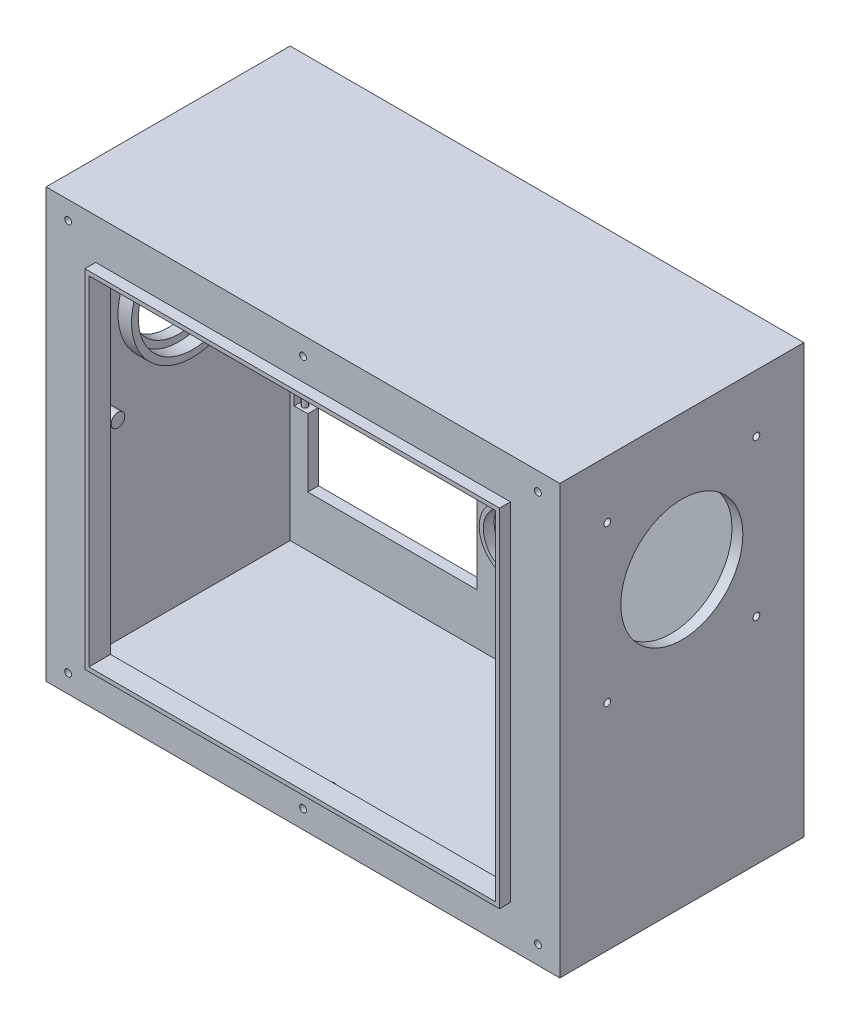
SolidWorks part; units mm, degrees
ref_plane "Alzado" through (0, 0, 0) normal (0, 0, 1) x (1, 0, 0)
ref_plane "Planta" through (0, 0, 0) normal (0, 1, 0) x (1, 0, 0)
ref_plane "Vista lateral" through (0, 0, 0) normal (1, 0, 0) x (0, 0, -1)
sketch "Croquis1" plane through (0, 0, 0) normal (0, 0, 1) x (1, 0, 0)
  line L0 (-189.5, 158) -> (189.5, 158)
  line L1 (-181.5, -150) -> (181.5, -150) construction
  line L2 (-181.5, -150) -> (-181.5, 150) construction
  line L3 (-181.5, 150) -> (181.5, 150) construction
  line L4 (181.5, -150) -> (181.5, 150) construction
  line L5 (-181.5, -150) -> (181.5, 150) construction
  line L6 (-181.5, 150) -> (181.5, -150) construction
  line L7 (189.5, -158) -> (189.5, 158)
  line L8 (-189.5, -158) -> (189.5, -158)
  line L9 (-189.5, -158) -> (-189.5, 158)
  point P0 (0, 0)
  dimension "D1" = 363
  dimension "D2" = 300
  dimension "D3" = 8
extrude "Saliente-Extruir1" add sketch "Croquis1" along normal blind 180
shell "Vaciado1" thickness 8 removed face at (0, 0, 180)
sketch "Croquis2" plane through (-189.5, 0, 0) normal (-1, 0, 0) x (0, 0, 1)
  line L0 (0, 158) -> (90, 158) construction
  line L1 (180, 158) -> (0, 158) construction
  circle A0 centre (90, 58) radius 35
extrude "Cortar-Extruir4" cut sketch "Croquis2" against normal blind 20 contours A0
sketch "Croquis4" plane through (-181.5, 0, 0) normal (1, 0, 0) x (0, 0, -1)
  circle A1 centre (-90, 58) radius 40
  circle A2 centre (-90, 58) radius 45
extrude "Saliente-Extruir4" add sketch "Croquis4" along normal blind 10
sketch "Croquis6" plane through (189.5, 0, 0) normal (1, 0, 0) x (0, 0, -1)
  line L0 (-90, 158) -> (-90, 58) construction
  line L1 (-180, 158) -> (0, 158) construction
  circle A0 centre (-90, 58) radius 45
  dimension "D1" = 90
extrude "Cortar-Extruir6" cut sketch "Croquis6" against normal blind 10 contours A0
sketch "Croquis7" plane through (0, 0, 8) normal (0, 0, 1) x (1, 0, 0)
  circle A3 centre (0, -53) radius 21
  circle A4 centre (0, -53) radius 24
  dimension "D1" = 42
  dimension "D2" = 48
extrude "Saliente-Extruir9" add sketch "Croquis7" along normal blind 18
ref_plane "Plano6" through (0, 0, 180) normal (0, 0, 1) x (1, 0, 0)
sketch "Croquis11" plane through (0, 0, 180) normal (0, 0, 1) x (1, 0, 0)
  line L1 (181.5, 150) -> (-181.5, 150)
  line L2 (181.5, 150) -> (181.5, -150)
  line L3 (181.5, -150) -> (-181.5, -150)
  line L4 (-181.5, 150) -> (-181.5, -150)
  line L5 (181.5, 150) -> (-181.5, -150) construction
  line L6 (181.5, -150) -> (-181.5, 150) construction
  line L7 (-150, 125) -> (150, 125)
  line L8 (-150, 125) -> (-150, -125)
  line L9 (-150, -125) -> (150, -125)
  line L10 (150, 125) -> (150, -125)
  line L11 (-150, 125) -> (150, -125) construction
  line L12 (-150, -125) -> (150, 125) construction
  point P0 (0, 0)
  point P7 (0, 0)
  dimension "D1" = 300
  dimension "D2" = 250
extrude "Saliente-Extruir10" add sketch "Croquis11" against normal blind 8
sketch "Croquis12" plane through (0, 0, 180) normal (0, 0, 1) x (1, 0, 0)
  line L1 (150, -125) -> (-150, -125)
  line L2 (150, -125) -> (150, 125)
  line L3 (150, 125) -> (-150, 125)
  line L4 (-150, -125) -> (-150, 125)
  line L5 (150, -125) -> (-150, 125) construction
  line L6 (150, 125) -> (-150, -125) construction
  line L7 (153, -128) -> (-153, -128)
  line L8 (153, -128) -> (153, 128)
  line L9 (153, 128) -> (-153, 128)
  line L10 (-153, -128) -> (-153, 128)
  line L11 (153, -128) -> (-153, 128) construction
  line L12 (153, 128) -> (-153, -128) construction
  point P0 (0, 0)
  point P8 (0, 0)
  dimension "D1" = 3
  dimension "D2" = 3
extrude "Saliente-Extruir11" add sketch "Croquis12" along normal blind 8
sketch "Croquis20" plane through (0, 0, 8) normal (0, 0, 1) x (1, 0, 0)
  circle A0 centre (0, -53) radius 18.5
  circle A1 centre (0, -53) radius 21
  circle A2 centre (0, -53) radius 21 construction
  dimension "D1" = 37
extrude "Saliente-Extruir19" add sketch "Croquis20" along normal blind 10
sketch "Croquis32" plane through (-181.5, 0, 0) normal (1, 0, 0) x (0, 0, -1)
  line L0 (-180, 158) -> (0, 158) construction
  line L1 (0, 158) -> (0, -158) construction
  line L2 (-35, 115.5) -> (-145, 115.5) construction
  line L3 (-35, 115.5) -> (-35, 0.5) construction
  line L4 (-35, 0.5) -> (-145, 0.5) construction
  line L5 (-145, 0.5) -> (-145, 115.5) construction
  circle A0 centre (-35, 115.5) radius 5
  circle A1 centre (-145, 115.5) radius 5
  circle A2 centre (-145, 0.5) radius 5
  circle A3 centre (-35, 0.5) radius 5
  dimension "D1" = 10
  dimension "D2" = 42.5
  dimension "D3" = 35
  dimension "D4" = 110
  dimension "D5" = 157.5
extrude "Saliente-Extruir22" add sketch "Croquis32" along normal blind 10
hole_wizard "Taladro roscado M63" positions "Croquis3D6" profile "Croquis26" tap size "M6" standard "DIN"
sketch3d "Croquis3D6"
  line L2 (-189.5, 0.5, 145) -> (-189.5, 115.5, 145) construction
  line L3 (-189.5, 0.5, 145) -> (-189.5, 0.5, 35) construction
  line L4 (-189.5, 0.5, 35) -> (-189.5, 115.5, 35) construction
  line L5 (-189.5, 115.5, 145) -> (-189.5, 115.5, 35) construction
  line L6 (-189.5, 0.5, 145) -> (-189.5, 115.5, 35) construction
  line L7 (-189.5, 0.5, 35) -> (-189.5, 115.5, 145) construction
  circle A1 centre (-189.5, 58, 90) radius 35 construction
  point P0 (-189.5, 115.5, 35)
  point P2 (-189.5, 115.5, 145)
  point P4 (-189.5, 0.5, 145)
  point P6 (-189.5, 0.5, 35)
  point P265 (-189.5, 58, 90)
  point P268 (-224.5, 58, 90)
  dimension "D1" = 115
  dimension "D2" = 0
  dimension "D3" = 110
cosmetic thread "Rosca de taladro1" parameters "D1"=12, "D2"=6
cosmetic thread "Rosca de taladro2" parameters "D1"=12, "D2"=6
cosmetic thread "Rosca de taladro3" parameters "D1"=12, "D2"=6
cosmetic thread "Rosca de taladro4" parameters "D1"=12, "D2"=6
sketch "Croquis26" plane through (-189.5, 115.5, 35) normal (0, 1, 0) x (0, 0, 1)
  line L0 (0, 0) -> (0, 15.5022)
  line L1 (0, 15.5022) -> (2.5, 14)
  line L2 (2.5, 14) -> (2.5, 0)
  line L5 (2.5, 0) -> (0, 0)
  line L10 (0, 15.5022) -> (-2.5, 14) construction
  line L11 (0, -6.35) -> (0, 107.95) construction
  dimension "Diámetro de perforador para roscar" = 5
  dimension "Profundidad de perforador para roscar" = 14
  dimension "Ángulo de perforador" = 118
sketch "Croquis27" plane through (0, 0, 0) normal (0, 0, -1) x (-1, 0, 0)
  circle A0 centre (0, -53) radius 11
  circle A1 centre (0, -53) radius 21 construction
  dimension "D1" = 22
sketch "Croquis28" plane through (0, 0, 0) normal (0, 0, -1) x (-1, 0, 0)
  line L0 (0, 0) -> (106, 0) construction
  line L5 (168.5, 112.5) -> (43.5, 112.5)
  line L6 (168.5, 112.5) -> (168.5, -112.5)
  line L11 (168.5, -112.5) -> (43.5, -112.5)
  line L12 (43.5, 112.5) -> (43.5, -112.5)
  line L13 (168.5, 112.5) -> (43.5, -112.5) construction
  line L14 (168.5, -112.5) -> (43.5, 112.5) construction
  point P0 (106, 0)
  dimension "D1" = 125
  dimension "D2" = 225
  dimension "D3" = 106
extrude "Cortar-Extruir7" cut sketch "Croquis28" against normal blind 8 contours L6 L5 L12 L11
sketch "Croquis29" plane through (0, 0, 0) normal (0, 0, -1) x (-1, 0, 0)
  line L1 (168.5, 112.5) -> (168.5, -112.5) construction
  line L2 (168.5, 62.5) -> (178.5, 62.5)
  line L3 (168.5, 62.5) -> (168.5, 42.5)
  line L4 (168.5, 42.5) -> (178.5, 42.5)
  line L5 (178.5, 62.5) -> (178.5, 42.5)
  line L6 (168.5, 62.5) -> (178.5, 42.5) construction
  line L7 (168.5, 42.5) -> (178.5, 62.5) construction
  line L8 (168.5, -42.5) -> (178.5, -42.5)
  line L9 (168.5, -42.5) -> (168.5, -62.5)
  line L10 (168.5, -62.5) -> (178.5, -62.5)
  line L11 (178.5, -42.5) -> (178.5, -62.5)
  line L12 (168.5, -42.5) -> (178.5, -62.5) construction
  line L13 (168.5, -62.5) -> (178.5, -42.5) construction
  point P0 (173.5, -52.5)
  point P2 (173.5, 52.5)
  dimension "D1" = 50
  dimension "D2" = 20
  dimension "D3" = 10
  dimension "D4" = 50
  dimension "D5" = 20
  dimension "D6" = 10
extrude "Cortar-Extruir9" cut sketch "Croquis29" against normal blind 8
sketch "Croquis30" plane through (0, 42.5, 0) normal (0, 1, 0) x (1, 0, 0)
  line L4 (-178.5, -8) -> (-178.5, 0) construction
  line L5 (-168.5, 0) -> (-178.5, 0) construction
  circle A1 centre (-174.5, -4) radius 2
  dimension "D1" = 4
  dimension "D2" = 4
  dimension "D3" = 4
extrude "Saliente-Extruir20" add sketch "Croquis30" along normal blind 9
sketch "Croquis31" plane through (0, -62.5, 0) normal (0, 1, 0) x (1, 0, 0)
  line L0 (-178.5, -8) -> (-178.5, 0) construction
  line L1 (-168.5, 0) -> (-178.5, 0) construction
  circle A0 centre (-174.5, -4) radius 2
  dimension "D3" = 4
  dimension "D1" = 4
  dimension "D2" = 4
extrude "Saliente-Extruir21" add sketch "Croquis31" along normal blind 9
mirror "Simetría1" about plane through (0, 0, 0) normal (1, 0, 0) of "Saliente-Extruir22"
sketch "Croquis33" plane through (0, 0, 180) normal (0, 0, 1) x (1, 0, 0)
  line L0 (-568.5, 474) -> (189.5, -158) construction
  line L2 (189.5, 158) -> (-189.5, -158) construction
  line L3 (0, 158) -> (0, -158) construction
  line L4 (189.5, 158) -> (-189.5, 158) construction
  line L5 (-189.5, -158) -> (189.5, -158) construction
  circle A0 centre (0, 144.5) radius 5
  circle A1 centre (0, -144.5) radius 5
  circle A2 centre (173.3085, -144.5) radius 5
  circle A3 centre (173.3085, 144.5) radius 5
  circle A4 centre (-173.3085, 144.5) radius 5
  circle A5 centre (-173.3085, -144.5) radius 5
  point P4 (-189.5, 158)
  dimension "D2" = 10
  dimension "D1" = 13.5
  dimension "D3" = 13.5
  dimension "D4" = 13.5
  dimension "D5" = 13.5
  dimension "D6" = 13.5
  dimension "D7" = 13.5
extrude "Saliente-Extruir23" add sketch "Croquis33" against normal blind 15 from surface starting at face at (0, 0, 172)
hole_wizard "Taladro roscado M64" positions "Croquis3D7" profile "Croquis35" tap size "M6" standard "DIN"
sketch3d "Croquis3D7"
  line L0 (-189.5, 158, 180) -> (189.5, -158, 180) construction
  line L2 (189.5, 158, 180) -> (-189.5, -158, 180) construction
  line L4 (0, 158, 180) -> (0, -158, 180) construction
  line L5 (189.5, 158, 180) -> (-189.5, 158, 180) construction
  line L6 (-189.5, -158, 180) -> (189.5, -158, 180) construction
  point P0 (-173.3085, 144.5, 180)
  point P2 (0, 144.5, 180)
  point P4 (173.3085, 144.5, 180)
  point P6 (173.3085, -144.5, 180)
  point P8 (0, -144.5, 180)
  point P10 (-173.3085, -144.5, 180)
  dimension "D1" = 13.5
  dimension "D2" = 13.5
  dimension "D3" = 13.5
  dimension "D4" = 13.5
  dimension "D5" = 13.5
  dimension "D6" = 13.5
sketch "Croquis35" plane through (-173.3085, 144.5, 180) normal (1, 0, 0) x (0, -1, 0)
  line L0 (0, 0) -> (0, 18.5022)
  line L1 (0, 18.5022) -> (2.5, 17)
  line L2 (2.5, 17) -> (2.5, 0)
  line L5 (2.5, 0) -> (0, 0)
  line L10 (0, 18.5022) -> (-2.5, 17) construction
  line L11 (0, -6.35) -> (0, 107.95) construction
  dimension "Diámetro de perforador para roscar" = 5
  dimension "Profundidad de perforador para roscar" = 17
  dimension "Ángulo de perforador" = 118
cosmetic thread "Rosca de taladro5" parameters "D1"=12, "D2"=6
cosmetic thread "Rosca de taladro6" parameters "D1"=12, "D2"=6
cosmetic thread "Rosca de taladro7" parameters "D1"=12, "D2"=6
cosmetic thread "Rosca de taladro8" parameters "D1"=12, "D2"=6
cosmetic thread "Rosca de taladro9" parameters "D1"=12, "D2"=6
cosmetic thread "Rosca de taladro10" parameters "D1"=12, "D2"=6
mirror "Simetría2" about plane through (0, 0, 0) normal (1, 0, 0) of "Taladro roscado M63"
cosmetic thread "Rosca de taladro11" parameters "D1"=12, "D2"=6
cosmetic thread "Rosca de taladro12" parameters "D1"=12, "D2"=6
cosmetic thread "Rosca de taladro13" parameters "D1"=12, "D2"=6
cosmetic thread "Rosca de taladro14" parameters "D1"=12, "D2"=6
